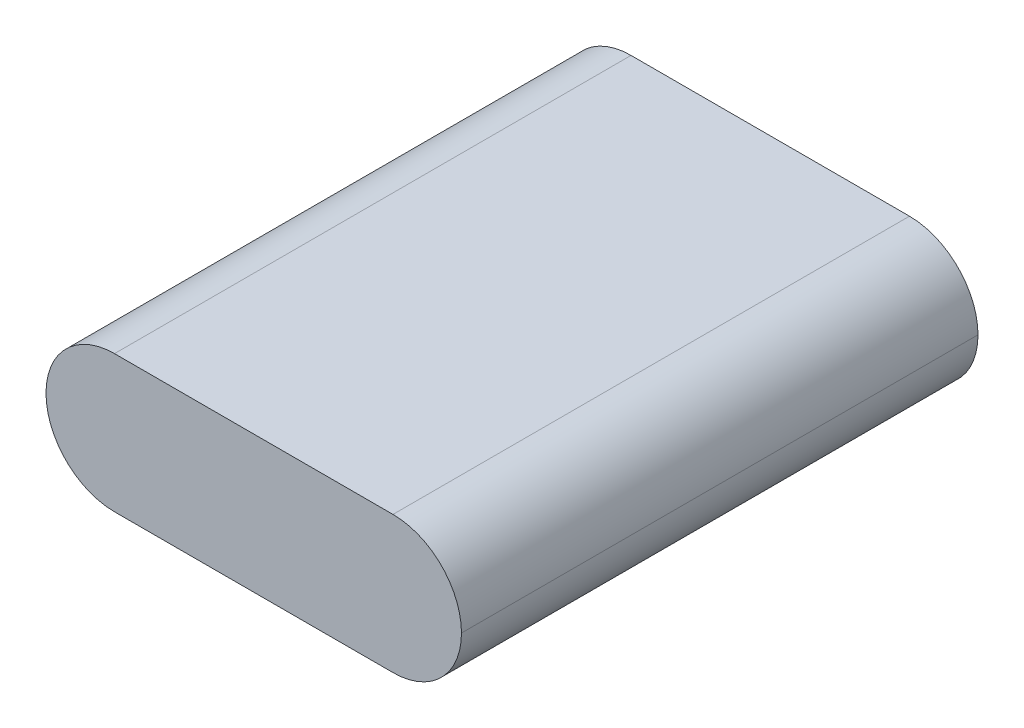
SolidWorks part; units mm, degrees
material "Nickel"
ref_plane "Front Plane" through (0, 0, 0) normal (0, 0, 1) x (1, 0, 0)
ref_plane "Top Plane" through (0, 0, 0) normal (0, 1, 0) x (1, 0, 0)
ref_plane "Right Plane" through (0, 0, 0) normal (1, 0, 0) x (0, 0, -1)
sketch "Sketch1" plane through (0, 0, 0) normal (0, 1, 0) x (1, 0, 0)
  line L1 (-27.75, 34.5) -> (27.75, 34.5)
  line L2 (-27.75, 34.5) -> (-27.75, -34.5)
  line L3 (-27.75, -34.5) -> (27.75, -34.5)
  line L4 (27.75, 34.5) -> (27.75, -34.5)
  line L5 (-27.75, 34.5) -> (27.75, -34.5) construction
  line L6 (-27.75, -34.5) -> (27.75, 34.5) construction
  point P0 (0, 0)
  dimension "D1" = 55.5
  dimension "D2" = 69
extrude "Boss-Extrude1" add sketch "Sketch1" along normal mid plane 18.3
fillet "Fillet1" radius 9.15 4 edges at (27.75, -9.15, 0) (27.75, 9.15, 0) (-27.75, -9.15, 0) (-27.75, 9.15, 0)
